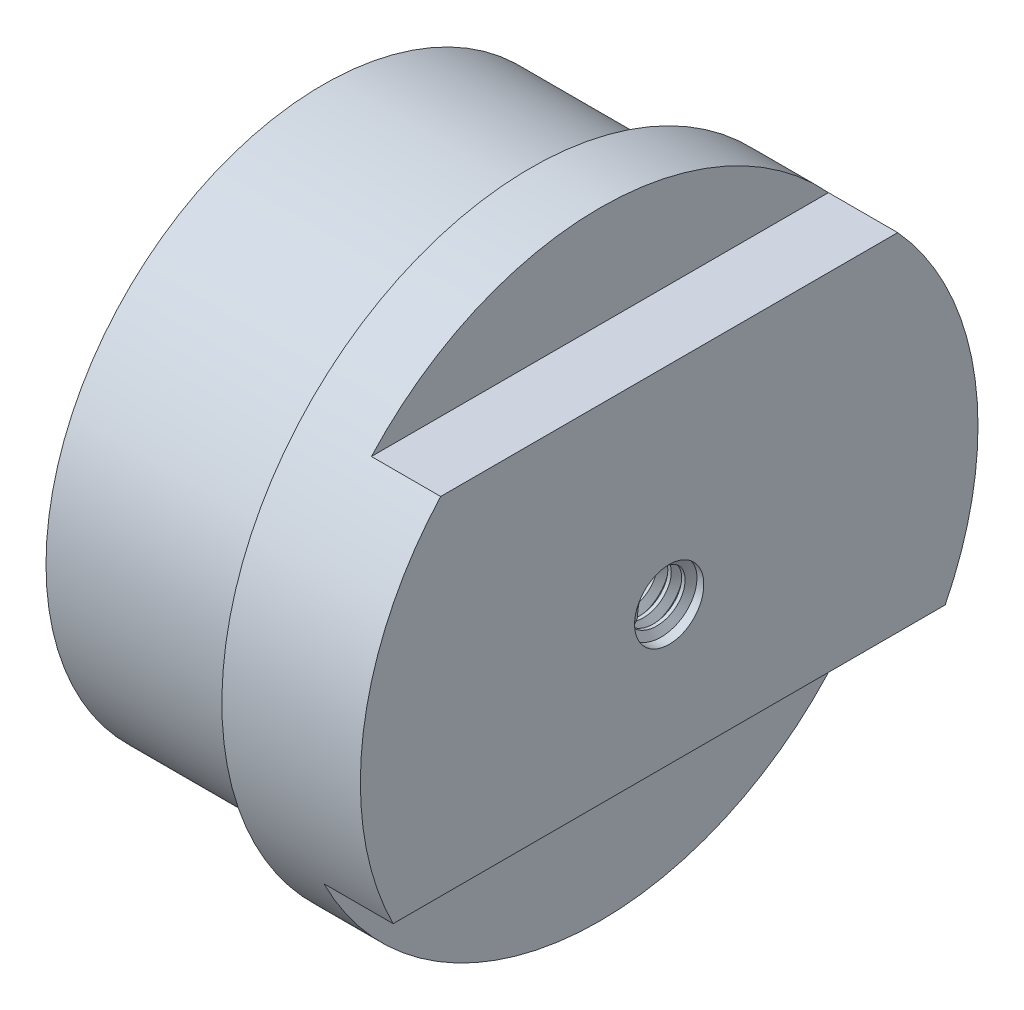
SolidWorks part; units mm, degrees
material "1060 Alloy"
ref_plane "Front Plane" through (0, 0, 0) normal (0, 0, 1) x (1, 0, 0)
ref_plane "Top Plane" through (0, 0, 0) normal (0, 1, 0) x (1, 0, 0)
ref_plane "Right Plane" through (0, 0, 0) normal (1, 0, 0) x (0, 0, -1)
sketch "Sketch1" plane through (0, 0, 0) normal (1, 0, 0) x (0, 0, -1)
  circle A0 centre (0, 0) radius 25.4
  dimension "D1" = 50.8
extrude "Boss-Extrude1" add sketch "Sketch1" along normal blind 19.05
sketch "Sketch2" plane through (19.05, 0, 0) normal (1, 0, 0) x (0, 0, -1)
  circle A0 centre (0, 0) radius 28.321
  dimension "D1" = 56.642
extrude "Boss-Extrude2" add sketch "Sketch2" along normal blind 6.35
sketch "Sketch3" plane through (25.4, 0, 0) normal (1, 0, 0) x (0, 0, -1)
  line L0 (0, 29.2816) -> (0, -32.1992) construction
  line L1 (-25.3138, -12.7) -> (25.3138, -12.7)
  line L2 (-20.9565, 19.05) -> (20.9565, 19.05)
  circle A0 centre (0, 0) radius 28.321 construction
  arc A1 (-20.9565, 19.05) -> (-25.3138, -12.7) centre (0, 0) ccw
  arc A2 (20.9565, 19.05) -> (25.3138, -12.7) centre (0, 0) cw
  dimension "D1" = 31.75
  dimension "D2" = 19.05
extrude "Boss-Extrude3" add sketch "Sketch3" along normal blind 6.35
sketch "Sketch4" plane through (31.75, 0, 0) normal (1, 0, 0) x (0, 0, -1)
  point P0 (0, 0)
hole_wizard "1/4 (0.25) Diameter Hole1" positions "Sketch4" profile "Sketch5" hole size "1/4" standard "ANSI Inch" end condition through all
sketch "Sketch5" plane through (31.75, 0, 0) normal (0, 1, 0) x (0, 0, -1)
  line L0 (0, 0) -> (0, 31.75)
  line L1 (0, 31.75) -> (3.175, 31.75)
  line L2 (3.175, 31.75) -> (3.175, 0)
  line L5 (3.175, 0) -> (0, 0)
  line L11 (0, -6.35) -> (0, 107.95) construction
  dimension "Thru Hole Dia." = 6.35
  dimension "Thru Hole Depth" = 31.75
thread "Thread1" pitch 1.27 method extrude profile "Thread Profile1" start angle 0, offset 0, length 0, pitch 1.27, diameter 6.35
ref_plane "Plane1" through (31.75, 0, 3.175) normal (0, -1, 0) x (0, 0, 1)
sketch "Thread Profile1" plane through (31.75, 0, 3.175) normal (0, -1, 0) x (0, 0, 1)
  line L0 (0, 0) -> (0, 1.27) construction
  line L11 (0, 0) -> (0, 1.1112)
  line L12 (0, 1.1112) -> (-0.6874, 0.7144)
  line L13 (-0.6874, 0.7144) -> (-0.6874, 0.3969)
  line L15 (-0.6874, 0.3969) -> (0, 0)
  line L17 (-0.6874, 0.5556) -> (0, 0.5556) construction
  point P2 (0, 0)
  dimension "Pitch" = 1.27
  dimension "Profile_Angle" = 60
  dimension "Profile_Land" = 0.3175
  dimension "Profile_Height" = 0.6874
